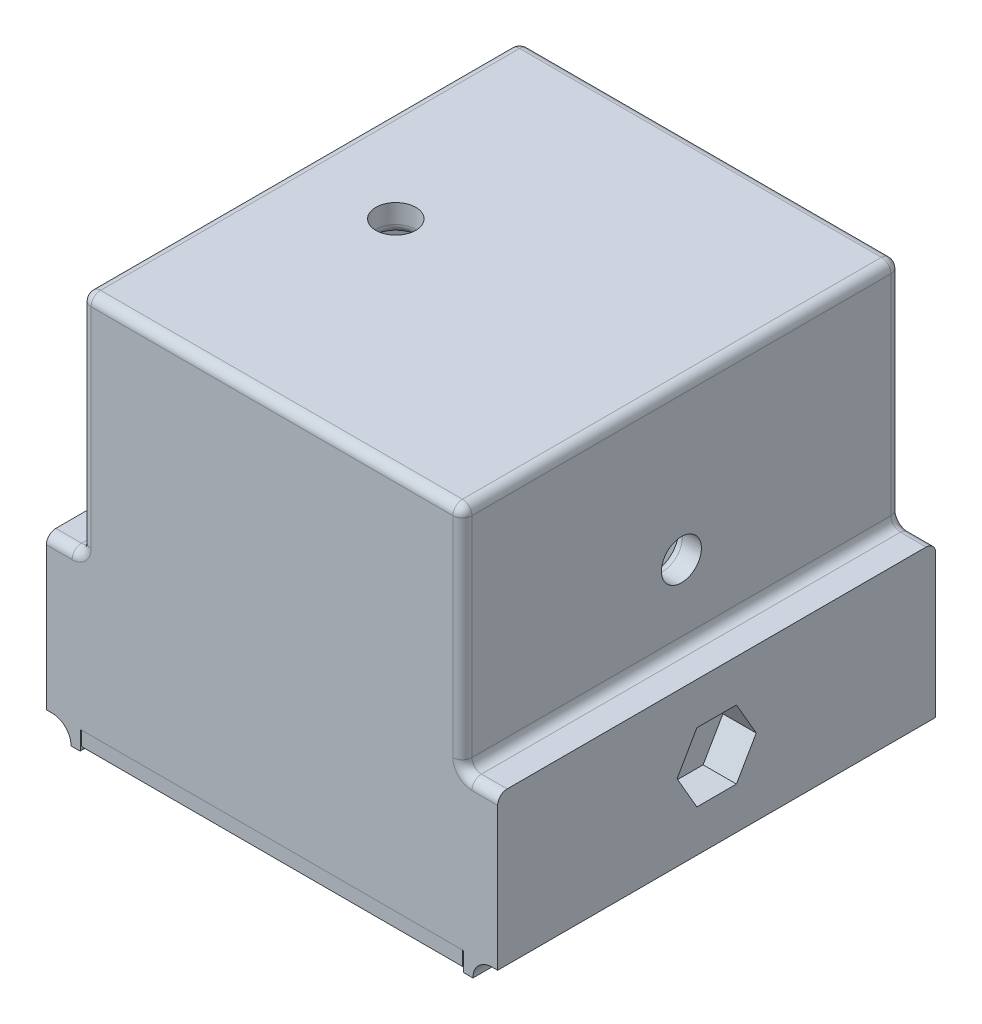
SolidWorks part; units mm, degrees
other "Gasket (DISABLE WHEN 3D PRINTING)" parameters "D1"=40, "D2"=18.2927
ref_plane "Front Plane" through (0, 0, 0) normal (0, 0, 1) x (1, 0, 0)
ref_plane "Top Plane" through (0, 0, 0) normal (0, 1, 0) x (1, 0, 0)
ref_plane "Right Plane" through (0, 0, 0) normal (1, 0, 0) x (0, 0, -1)
sketch "Sketch1" plane through (0, 0, 0) normal (0, 1, 0) x (1, 0, 0)
  line L1 (-20, 23) -> (20, 23)
  line L2 (-20, 23) -> (-20, -23)
  line L3 (-20, -23) -> (20, -23)
  line L4 (20, 23) -> (20, -23)
  line L5 (-20, 23) -> (20, -23) construction
  line L6 (-20, -23) -> (20, 23) construction
  point P4 (0, 0)
  dimension "D1" = 40
  dimension "D2" = 46
extrude "Body" add sketch "Sketch1" along normal blind 40
sketch "Sketch2" plane through (0, 0, 0) normal (0, 1, 0) x (1, 0, 0)
  line L0 (0, -24.6326) -> (0, 25.7324) construction
  line L1 (-20, -23) -> (-23.7, -23)
  line L2 (-20, -23) -> (-20, 23)
  line L3 (-20, 23) -> (-23.7, 23)
  line L4 (-23.7, -23) -> (-23.7, 23)
  line L5 (-20, -23) -> (-23.7, 23) construction
  line L6 (-20, 23) -> (-23.7, -23) construction
  line L7 (20, 23) -> (23.7, 23)
  line L8 (23.7, -23) -> (23.7, 23)
  line L9 (20, -23) -> (23.7, -23)
  line L10 (20, -23) -> (20, 23)
  point P4 (-21.85, 0)
  dimension "D1" = 3.7
extrude "Extension" add sketch "Sketch2" along normal blind 16
sketch "Nut Alignment Sketch" plane through (0, 0, 0) normal (1, 0, 0) x (0, 0, -1)
  line L0 (-23, 16) -> (23, 0) construction
  circle A0 centre (0, 8) radius 2.5 construction
  dimension "D1" = 5
sketch "Sketch5" plane through (0, 0, 0) normal (0, 1, 0) x (1, 0, 0)
  line L1 (-17, -20) -> (17, -20)
  line L2 (-17, -20) -> (-17, 20)
  line L3 (-17, 20) -> (17, 20)
  line L4 (17, -20) -> (17, 20)
  line L5 (-17, -20) -> (17, 20) construction
  line L6 (-17, 20) -> (17, -20) construction
  line L7 (-20, 23) -> (-20, -23) construction
  line L8 (-23.7, -23) -> (23.7, -23) construction
  line L9 (-20, 23) -> (-20, -23) construction
  point P4 (0, 0)
  dimension "D1" = 3
  dimension "D2" = 3
extrude "Cavity" cut sketch "Sketch5" along normal blind 37
sketch "Sketch6" plane through (0, 40, 0) normal (0, 1, 0) x (1, 0, 0)
  line L0 (0, 5.2625) -> (0, 72.0397) construction
  line L1 (-26.607, 0) -> (21.944, 0) construction
  circle A0 centre (-10, 0) radius 2.1
  dimension "D2" = 4.2
  dimension "D1" = 10
extrude "Top Hole" cut sketch "Sketch6" against normal up to next
sketch "Sketch7" plane through (20, 0, 0) normal (1, 0, 0) x (0, 0, -1)
  line L0 (-23, 28) -> (23, 28) construction
  line L1 (-23, 40) -> (-23, 16) construction
  line L2 (23, 40) -> (23, 16) construction
  line L4 (0, 41.5439) -> (0, 6.2839) construction
  circle A0 centre (0, 24) radius 2.1
  dimension "D2" = 4.2
  dimension "D1" = 4
extrude "Side Hole" cut sketch "Sketch7" against normal up to next
sketch "Sketch3" plane through (0, 0, 0) normal (0, 1, 0) x (1, 0, 0)
  line L0 (-23.7, -23) -> (23.7, -23) construction
  line L1 (-21.1, -23) -> (-20.1, -23)
  line L2 (-21.1, -23) -> (-21.1, 23)
  line L3 (-21.1, 23) -> (-20.1, 23)
  line L4 (-20.1, -23) -> (-20.1, 23)
  line L5 (-21.1, -23) -> (-20.1, 23) construction
  line L6 (-21.1, 23) -> (-20.1, -23) construction
  line L7 (23.7, 23) -> (-23.7, 23) construction
  line L8 (0, -26.2727) -> (0, 27.5208) construction
  line L9 (-23.7, 23) -> (-23.7, -23) construction
  line L10 (23.7, -23) -> (23.7, 23) construction
  line L11 (21.1, 23) -> (20.1, 23)
  line L12 (20.1, -23) -> (20.1, 23)
  line L13 (21.1, -23) -> (20.1, -23)
  line L14 (21.1, -23) -> (21.1, 23)
  point P4 (-20.6, 0)
  dimension "D1" = 1
  dimension "D2" = 20.1
  dimension "D3" = 23.7
  dimension "D4" = 23.7
extrude "Legs" add sketch "Sketch3" against normal blind 2
sketch "Sketch4" plane through (-23.7, 0, 0) normal (-1, 0, 0) x (0, 0, 1)
  line L0 (-23, 16) -> (23, 0) construction
  line L2 (2.0785, 11.6) -> (-2.0785, 11.6)
  line L3 (-2.0785, 11.6) -> (-4.1569, 8)
  line L4 (-4.1569, 8) -> (-2.0785, 4.4)
  line L5 (-2.0785, 4.4) -> (2.0785, 4.4)
  line L6 (2.0785, 4.4) -> (4.1569, 8)
  line L7 (4.1569, 8) -> (2.0785, 11.6)
  circle A0 centre (0, 8) radius 3.6 construction
  dimension "D1" = 7.2
extrude "Mount Counterbore" cut sketch "Sketch4" against normal blind 3.5
mirror "Mount Counterbore Mirror" about plane through (0, 0, 0) normal (1, 0, 0) of "Mount Counterbore"
fillet "2mm Leg Fillet" radius 2 2 edges at (21.1, 0, 0) (-21.1, 0, 0)
fillet "0.1mm Leg Fillet" radius 0.1 4 edges at (-20.1, -2, 0) (-20.1, 0, 0) (20.1, -2, 0) (20.1, 0, 0)
fillet "Outer Boundary Fillet" radius 1 14 edges at (-20, 16, 0) (-21.85, 16, -23) (-20, 28, -23) (-20, 40, 0) (0, 40, -23) (20, 40, 0) (20, 28, -23) (21.85, 16, -23) (20, 16, 0) (-21.85, 16, 23) (-20, 28, 23) (0, 40, 23) (20, 28, 23) (21.85, 16, 23)
fillet "Inner Boundary Fillet" radius 1 10 edges at (-10, 37, -2.1) (17, 24, 2.1) (17, 18.5, -20) (-17, 18.5, 20) (-17, 18.5, -20) (0, 37, -20) (-17, 37, 0) (0, 37, 20) (17, 37, 0) (17, 18.5, 20)
sketch "Sketch8" plane through (0, 0, 0) normal (0, -1, 0) x (1, 0, 0)
  line L4 (-16, -20) -> (16, -20)
  line L5 (-17, 19) -> (-17, -19)
  line L6 (16, 20) -> (-16, 20)
  line L7 (17, -19) -> (17, 19)
  line L8 (-16, -20) -> (16, -20)
  line L9 (-17, 19) -> (-17, -19)
  line L10 (16, 20) -> (-16, 20)
  line L11 (17, -19) -> (17, 19)
  line L12 (-20, -23) -> (20, -23)
  line L13 (20, -23) -> (20, 23)
  line L14 (20, 23) -> (-20, 23)
  line L15 (-20, 23) -> (-20, -23)
  line L16 (-20, -23) -> (20, -23)
  line L17 (20, -23) -> (20, 23)
  line L18 (20, 23) -> (-20, 23)
  line L19 (-20, 23) -> (-20, -23)
  arc A4 (-17, -19) -> (-16, -20) centre (-16, -19) ccw
  arc A5 (-16, 20) -> (-17, 19) centre (-16, 19) ccw
  arc A6 (17, 19) -> (16, 20) centre (16, 19) ccw
  arc A7 (16, -20) -> (17, -19) centre (16, -19) ccw
  arc A8 (-17, -19) -> (-16, -20) centre (-16, -19) ccw
  arc A9 (-16, 20) -> (-17, 19) centre (-16, 19) ccw
  arc A10 (17, 19) -> (16, 20) centre (16, 19) ccw
  arc A11 (16, -20) -> (17, -19) centre (16, -19) ccw
  dimension "D1" = 0
  dimension "D2" = 0
extrude "Boss-Extrude1" add sketch "Sketch8" along normal blind 1.5 separate body
equation "\"Height\"= 40mm"
equation "\"D1@Body\"=\"Height\""
equation "\"Length\"= 40mm"
equation "\"Width\"= 46"
equation "\"D2@Sketch1\"=\"Width\""
equation "\"D1@Sketch1\"=\"Length\""
equation "\"D1@Cavity\" = \"Height\" - 3mm"
